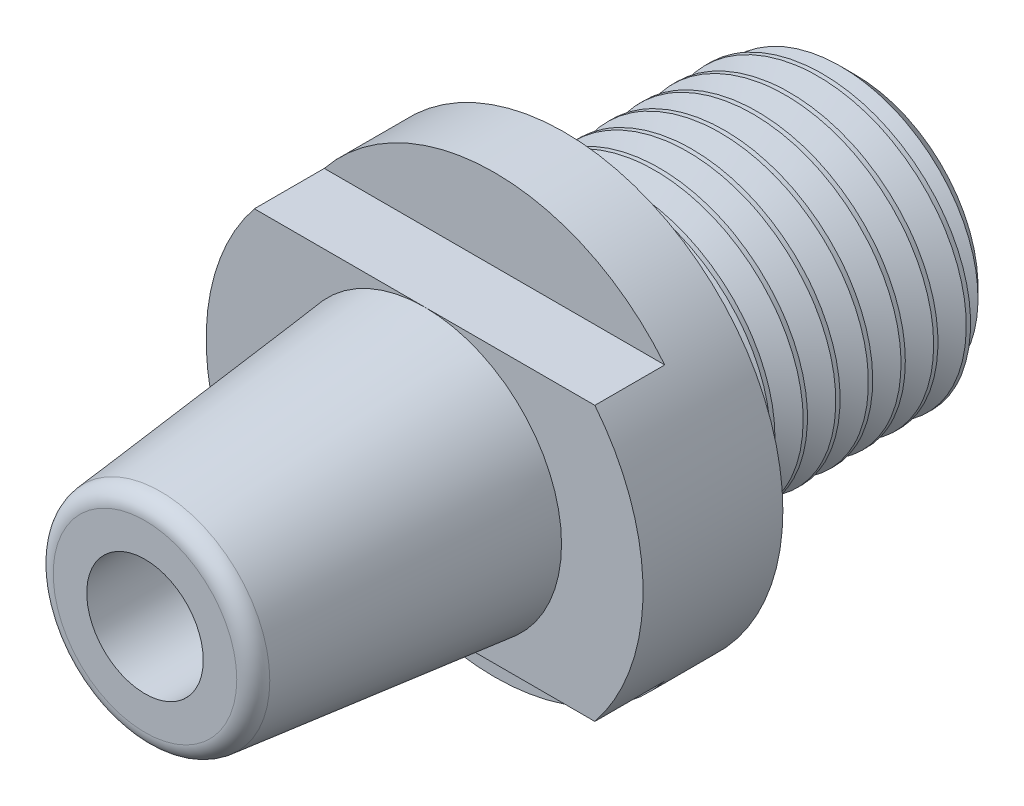
SolidWorks part; units mm, degrees
ref_plane "Front Plane" through (0, 0, 0) normal (0, 0, 1) x (1, 0, 0)
ref_plane "Top Plane" through (0, 0, 0) normal (0, 1, 0) x (1, 0, 0)
ref_plane "Right Plane" through (0, 0, 0) normal (1, 0, 0) x (0, 0, -1)
sketch "Sketch1" plane through (0, 0, 0) normal (0, 0, 1) x (1, 0, 0)
  circle A0 centre (0, 0) radius 2.1
  dimension "D1" = 4.2
extrude "Boss-Extrude1" add sketch "Sketch1" along normal blind 5
sketch "Sketch2" plane through (0, 0, 0) normal (0, 0, -1) x (-1, 0, 0)
  circle A0 centre (0, 0) radius 2.5
  dimension "D1" = 5
extrude "Boss-Extrude2" add sketch "Sketch2" against normal blind 4.5
chamfer "Chamfer1" distance 0.4 angle 45 1 edges at (-2.5, 0, 0)
sketch "Sketch3" plane through (0, 0, 5) normal (0, 0, 1) x (1, 0, 0)
  circle A0 centre (0, 0) radius 3.75
  dimension "D1" = 7.5
extrude "Boss-Extrude3" add sketch "Sketch3" along normal blind 2.4
sketch "Sketch4" plane through (0, 0, 7.4) normal (0, 0, 1) x (1, 0, 0)
  line L0 (0, 2.35) -> (0, 3.75) construction
  line L1 (-4.6983, 5.1316) -> (4.6983, 5.1316)
  line L2 (-4.6983, 5.1316) -> (-4.6983, 2.35)
  line L3 (-4.6983, 2.35) -> (4.6983, 2.35)
  line L4 (4.6983, 5.1316) -> (4.6983, 2.35)
  circle A0 centre (0, 0) radius 3.75 construction
  dimension "D1" = 1.4
extrude "Cut-Extrude1" cut sketch "Sketch4" against normal blind 1.2
mirror "Mirror1" about plane through (0, 0, 0) normal (0, 1, 0) of "Cut-Extrude1"
sketch "Sketch5" plane through (0, 0, 7.4) normal (0, 0, 1) x (1, 0, 0)
  circle A0 centre (0, 0) radius 2.35
  dimension "D1" = 4.7
extrude "Boss-Extrude4" add sketch "Sketch5" along normal blind 4.8 draft 6
sketch "Sketch6" plane through (0, 0, 12.2) normal (0, 0, 1) x (1, 0, 0)
  circle A0 centre (0, 0) radius 1
  circle A1 centre (0, 0) radius 1.8455 construction
  dimension "D1" = 2
extrude "Cut-Extrude2" cut sketch "Sketch6" against normal blind 10.8
sketch "Sketch7" plane through (0, 0, 0) normal (0, 0, -1) x (-1, 0, 0)
  circle A0 centre (0, 0) radius 0.5
  dimension "D1" = 1
extrude "Cut-Extrude3" cut sketch "Sketch7" against normal blind 6.2
fillet "Fillet1" radius 0.3 1 edges at (1.8455, 0, 12.2)
sketch "Sketch8" plane through (0, 0, 0) normal (0, 0, -1) x (-1, 0, 0)
  circle A0 centre (0, 0) radius 2.5 construction
  circle A1 centre (0, 0) radius 2.5
curve "Helix/Spiral1" pitch 0.56 height 4.48 turns 8
ref_plane "Plane1" through (-2.5, 0, 0) normal (0, -0.9994, 0.0356) x (-1, 0, 0)
sketch "Sketch9" plane through (-2.5, 0, 0) normal (0, -0.9994, 0.0356) x (-1, 0, 0)
  line L0 (0.4223, -7.479) -> (0.4223, -6.2798) construction
  line L1 (-0.4208, -0.0063) -> (0.0555, -0.2813)
  line L2 (0.0555, -0.2813) -> (0.0555, 0.2687)
  line L3 (0.0555, 0.2687) -> (-0.4208, -0.0063)
  circle A0 centre (-0.1033, -0.0063) radius 0.1588 construction
  dimension "D1" = 0.55
sweep "Cut-Sweep1" cut profiles "Sketch9" path "Helix/Spiral1"
